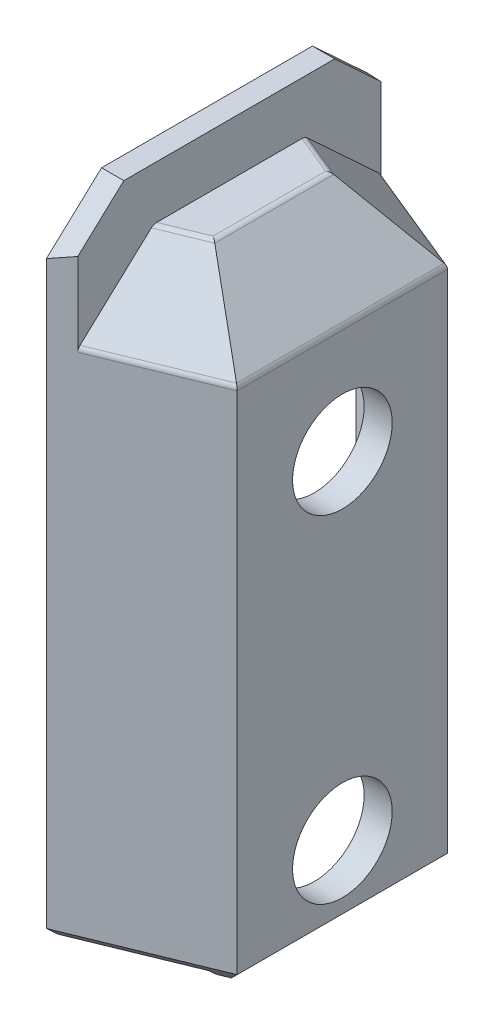
SolidWorks part; units mm, degrees
material "PLA"
ref_plane "Front Plane" through (0, 0, 0) normal (0, 0, 1) x (1, 0, 0)
ref_plane "Top Plane" through (0, 0, 0) normal (0, 1, 0) x (1, 0, 0)
ref_plane "Right Plane" through (0, 0, 0) normal (1, 0, 0) x (0, 0, -1)
sketch "Sketch1" plane through (0, 0, 0) normal (1, 0, 0) x (0, 0, -1)
  line L1 (-15, 2.5) -> (15, 2.5)
  line L2 (-15, 2.5) -> (-15, -2.5)
  line L3 (-15, -2.5) -> (15, -2.5)
  line L4 (15, 2.5) -> (15, -2.5)
  point P4 (0, 2.5)
  point P6 (-15, 0)
  dimension "D1" = 30
  dimension "D2" = 5
extrude "Boss-Extrude1" add sketch "Sketch1" along normal blind 19.3
sketch "Sketch2" plane through (0, 0, 0) normal (-1, 0, 0) x (0, 0, 1)
  line L0 (-20.4312, -2.5) -> (20.4312, -2.5) construction
  line L4 (15, 0) -> (20.5974, 0) construction
  line L5 (-19.4026, -2.5) -> (20.5974, -2.5)
  line L7 (-19.4026, 7.5) -> (20.5974, 7.5)
  line L8 (20.5974, -2.5) -> (20.5974, 7.5)
  line L9 (-19.4026, 7.5) -> (-19.4026, 2.5) construction
  line L11 (-19.4026, 7.5) -> (-19.4026, -2.5)
  line L12 (-19.4026, 0) -> (-15, 0) construction
  line L13 (-15, -2.5) -> (-15, 2.5) construction
  line L14 (15, 2.5) -> (15, -2.5) construction
  line L15 (-19.4026, 5) -> (0, 5) construction
  line L16 (20.5974, 5) -> (0, 5) construction
  point P3 (0, -2.5)
  point P6 (0, 2.5)
  point P12 (0, 0)
  dimension "D1" = 10
  dimension "D2" = 40
extrude "Boss-Extrude2" add sketch "Sketch2" against normal blind 3.175
sketch "Sketch3" plane through (0, -2.5, 0) normal (0, -1, 0) x (1, 0, 0)
  line L0 (19.3, -15) -> (3.175, -15) construction
  line L1 (19.3, 15) -> (15.3, 15)
  line L2 (19.3, 15) -> (19.3, -15)
  line L3 (19.3, -15) -> (15.3, -15)
  line L4 (15.3, 15) -> (15.3, -15)
  dimension "D1" = 4
extrude "Boss-Extrude3" add sketch "Sketch3" along normal blind 75
sketch "Sketch4" plane through (19.3, 0, 0) normal (1, 0, 0) x (0, 0, -1)
  line L0 (15, 2.5) -> (-15, 2.5) construction
  circle A0 centre (0, -17.9) radius 7.1
  circle A1 centre (0, -65.9) radius 7.1
  dimension "D1" = 14.2
  dimension "D2" = 14.2
  dimension "D3" = 20.4
  dimension "D4" = 48
extrude "Cut-Extrude1" cut sketch "Sketch4" against normal up to next
sketch "Sketch10" plane through (0, 2.5, 0) normal (0, 1, 0) x (1, 0, 0)
  line L0 (3.175, 19.4026) -> (0, 19.4026)
  line L1 (0, 19.4026) -> (0, 22.9026)
  line L2 (0, 22.9026) -> (19.3, 15)
  line L3 (19.3, 15) -> (3.175, 15) construction
  line L4 (19.3, 15) -> (19.3, -15) construction
  line L5 (3.175, 19.4026) -> (3.175, 15)
  line L6 (3.175, 15) -> (19.3, 15)
  dimension "D1" = 3.5
extrude "Boss-Extrude7" add sketch "Sketch10" against normal up to surface (5 mm away) up to face at (5.4125, -2.5, 0.2987)
sketch "Sketch11" plane through (0, 2.5, 0) normal (0, 1, 0) x (1, 0, 0)
  line L0 (0, 19.4026) -> (0, 22.9026)
  line L1 (0, 22.9026) -> (3.175, 21.6026)
  line L2 (19.3, 15) -> (0, 22.9026) construction
  line L3 (3.175, 21.6026) -> (3.175, 19.4026)
  line L4 (3.175, 19.4026) -> (0, 19.4026)
extrude "Boss-Extrude8" add sketch "Sketch11" along normal up to surface (5 mm away) up to face at (1.5875, 7.5, 0.5974)
ref_plane "Plane1" through (0, 0, 0) normal (0, 0, -1) x (-1, 0, 0)
mirror "Mirror2" about plane through (0, 0, 0) normal (0, 0, -1) of "Boss-Extrude8", "Boss-Extrude7"
chamfer "Chamfer1" distance 5 angle 45 1 edges at (3.175, 2.5, 0)
sketch "Sketch12" plane through (0, -2.5, 0) normal (0, -1, 0) x (1, 0, 0)
  line L0 (0, -22.9026) -> (19.3, -15)
  line L1 (19.3, -15) -> (15.3, -15)
  line L2 (15.3, -15) -> (0, -21.2648)
  line L3 (0, 22.9026) -> (0, -22.9026) construction
  line L4 (0, -21.2648) -> (0, -22.9026)
  line L5 (0, 22.9026) -> (19.3, 15)
  line L6 (19.3, 15) -> (15.3, 15)
  line L7 (15.3, 15) -> (0, 21.2648)
  line L8 (0, 21.2648) -> (0, 22.9026)
extrude "Boss-Extrude9" add sketch "Sketch12" along normal up to surface (75 mm away) up to face at (17.3, -77.5, 0)
sketch "Sketch13" plane through (0, 2.5, 0) normal (0, 1, 0) x (1, 0, 0)
  line L0 (3.175, 21.6026) -> (3.175, -21.6026)
  line L1 (3.175, -21.6026) -> (19.3, -15)
  line L2 (19.3, -15) -> (19.3, 15)
  line L3 (19.3, 15) -> (3.175, 21.6026)
extrude "Boss-Extrude10" add sketch "Sketch13" along normal up to surface (5 mm away) up to face at (1.5875, 7.5, 0)
chamfer "Chamfer2" distance 5 angle 45 3 edges at (7.65, -2.5, 18.1324) (7.65, -2.5, -18.1324) (15.3, -2.5, 0)
chamfer "Chamfer3" distance 10 angle 45 3 edges at (9.65, 7.5, -18.9513) (9.65, 7.5, 18.9513) (19.3, 7.5, 0)
sketch "Sketch14" plane through (0, 0, 0) normal (-1, 0, 0) x (0, 0, 1)
  line L15 (-22.9026, -2.5) -> (-22.9026, 7.7188)
  line L16 (22.9026, -2.5) -> (22.9026, 7.7188)
  line L18 (27.9967, 3.0046) -> (15.0346, 15)
  line L19 (15.0346, 15) -> (-15.0346, 15)
  line L20 (-15.0346, 15) -> (-27.9967, 3.0046)
  line L21 (22.9026, 7.7188) -> (15.0346, 15)
  line L22 (15.0346, 15) -> (-15.0346, 15)
  line L23 (-15.0346, 15) -> (-22.9026, 7.7188)
  line L29 (-22.9026, -2.5) -> (22.9026, -2.5)
  dimension "D1" = 7.5
extrude "Boss-Extrude15" add sketch "Sketch14" against normal blind 3.175
sketch "Sketch15" plane through (0, -2.5, 0) normal (0, -1, 0) x (1, 0, 0)
  line L3 (3.175, 22.9026) -> (0, 22.9026)
  line L4 (0, 22.9026) -> (3.175, 21.6026)
  line L5 (3.175, 21.6026) -> (3.175, 22.9026)
  line L6 (3.175, 22.9026) -> (0, 22.9026)
  line L7 (0, 22.9026) -> (3.175, 21.6026)
  line L8 (3.175, 21.6026) -> (3.175, 22.9026)
  line L9 (3.175, -22.9026) -> (3.175, -21.6026)
  line L10 (3.175, -21.6026) -> (0, -22.9026)
  line L11 (0, -22.9026) -> (3.175, -22.9026)
  line L12 (3.175, -22.9026) -> (3.175, -21.6026)
  line L13 (3.175, -21.6026) -> (0, -22.9026)
  line L14 (0, -22.9026) -> (3.175, -22.9026)
  dimension "D1" = 0
  dimension "D2" = 0
extrude "Cut-Extrude2" cut sketch "Sketch15" against normal through all
fillet "Fillet6" radius 1 3 edges at (6.2375, 7.5, -9.5428) (9.3, 7.5, 0) (6.2375, 7.5, 9.5428)
fillet "Fillet7" radius 1 3 edges at (11.2375, -2.5, -18.3013) (19.3, -2.5, 0) (11.2375, -2.5, 18.3013)
chamfer "Chamfer6" distance 2.5 angle 45 3 edges at (9.65, -77.5, -18.9513) (19.3, -77.5, 0) (9.65, -77.5, 18.9513)
